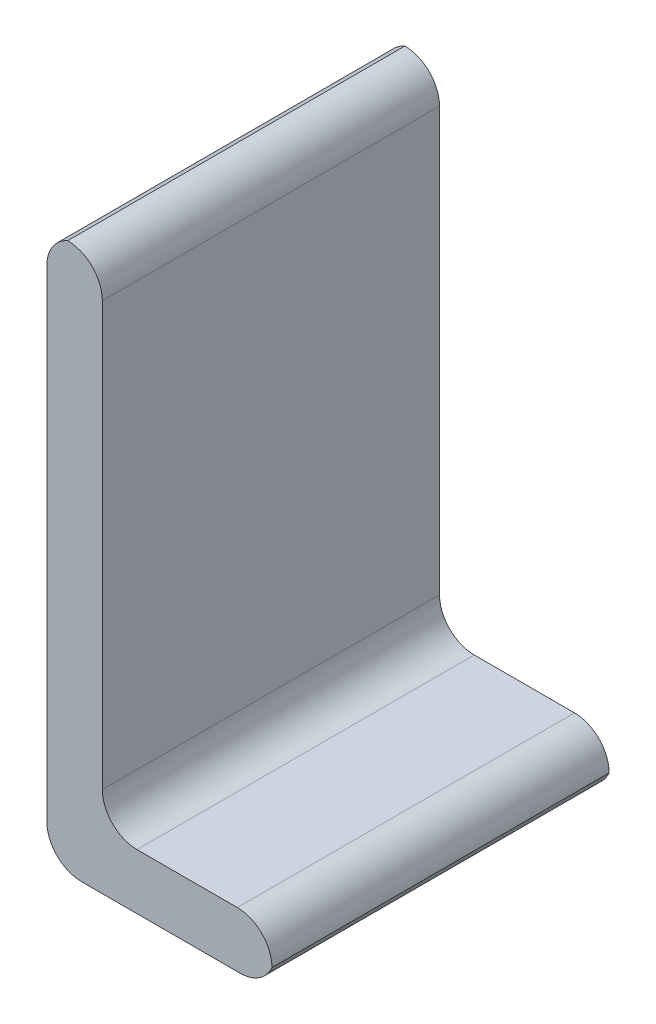
SolidWorks part; units mm, degrees
material "ABS"
ref_plane "X-Y Datum" through (0, 0, 0) normal (0, 0, 1) x (1, 0, 0)
ref_plane "X-Z Datum" through (0, 0, 0) normal (0, 1, 0) x (1, 0, 0)
ref_plane "Y-Z Datum" through (0, 0, 0) normal (1, 0, 0) x (0, 0, -1)
sketch "Sketch2" plane through (0, 0, 0) normal (0, 0, 1) x (1, 0, 0)
  line L0 (0, 5) -> (0, 74.46)
  line L3 (8, 0) -> (27.8774, 0)
  line L4 (5, 0) -> (8, 0)
  line L5 (8, 74.0426) -> (8, 13)
  line L6 (13, 8) -> (27.46, 8)
  arc A0 (13, 8) -> (8, 13) centre (13, 13) cw
  arc A1 (5, 0) -> (0, 5) centre (5, 5) cw
  arc A2 (3, 79.0426) -> (0, 74.46) centre (5, 74.46) ccw
  arc A3 (3, 79.0426) -> (8, 74.0426) centre (3, 74.0426) cw
  arc A4 (32.46, 3) -> (27.8774, 0) centre (27.8774, 5) cw
  arc A5 (32.46, 3) -> (27.46, 8) centre (27.46, 3) ccw
  point P12 (0, 0)
  dimension "D1" = 5
  dimension "D2" = 5
  dimension "D3" = 5
  dimension "D4" = 5
  dimension "D5" = 5
  dimension "D6" = 69.46
  dimension "D7" = 8
  dimension "D8" = 8
  dimension "D9" = 32.46
extrude "Boss-Extrude1" add sketch "Sketch2" along normal blind 48.62
